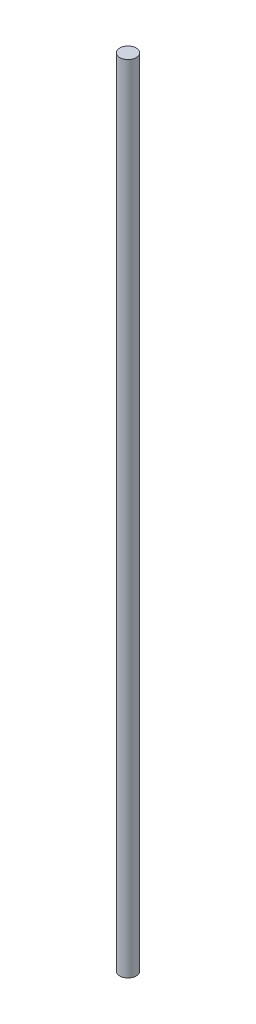
SolidWorks part; units mm, degrees
ref_plane "Front Plane" through (0, 0, 0) normal (0, 0, 1) x (1, 0, 0)
ref_plane "Top Plane" through (0, 0, 0) normal (0, 1, 0) x (1, 0, 0)
ref_plane "Right Plane" through (0, 0, 0) normal (1, 0, 0) x (0, 0, -1)
sketch "Sketch1" plane through (0, 0, 0) normal (0, 1, 0) x (1, 0, 0)
  circle A0 centre (0, 0) radius 1.5875
  dimension "D1" = 3.175
extrude "Boss-Extrude1" add sketch "Sketch1" along normal blind 152.4
